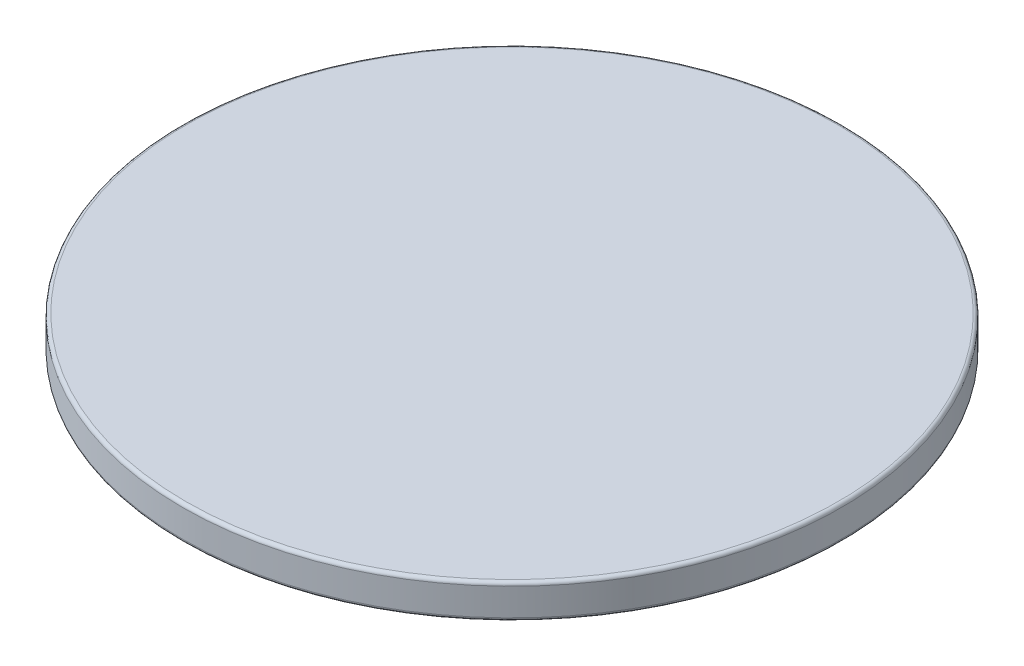
SolidWorks part; units mm, degrees
ref_plane "Front" through (0, 0, 0) normal (0, 0, 1) x (1, 0, 0)
ref_plane "Top" through (0, 0, 0) normal (0, 1, 0) x (1, 0, 0)
ref_plane "Right" through (0, 0, 0) normal (1, 0, 0) x (0, 0, -1)
sketch "Sketch2" plane through (0, 0, 0) normal (0, 1, 0) x (1, 0, 0)
  circle A0 centre (0, 0) radius 61.214
  dimension "D1" = 122.428
extrude "Boss-Extrude1" add sketch "Sketch2" along normal blind 6.35
fillet "Fillet1" radius 0.635 2 edges at (0, 0, 61.214) (0, 6.35, 61.214)
